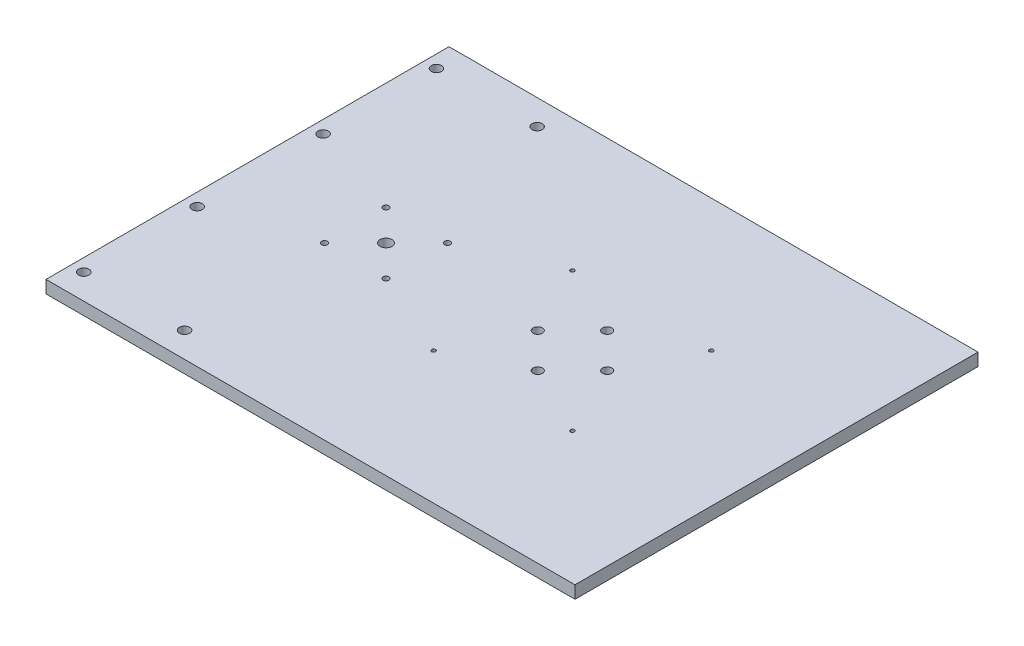
SolidWorks part; units mm, degrees
ref_plane "Front Plane" through (0, 0, 0) normal (0, 0, 1) x (1, 0, 0)
ref_plane "Top Plane" through (0, 0, 0) normal (0, 1, 0) x (1, 0, 0)
ref_plane "Right Plane" through (0, 0, 0) normal (1, 0, 0) x (0, 0, -1)
sketch "Sketch1" plane through (0, 0, 0) normal (0, 1, 0) x (1, 0, 0)
  line L1 (-133.35, -101.6) -> (133.35, -101.6)
  line L2 (-133.35, -101.6) -> (-133.35, 101.6)
  line L3 (-133.35, 101.6) -> (133.35, 101.6)
  line L4 (133.35, -101.6) -> (133.35, 101.6)
  line L5 (-133.35, -101.6) -> (133.35, 101.6) construction
  line L6 (-133.35, 101.6) -> (133.35, -101.6) construction
  point P0 (0, 0)
  dimension "D1" = 203.2
  dimension "D2" = 266.7
extrude "Boss-Extrude1" add sketch "Sketch1" along normal blind 6.35
sketch "Sketch2" plane through (0, 0, 0) normal (0, 1, 0) x (1, 0, 0)
  line L0 (-193.2668, 0) -> (192.9727, 0) construction
sketch "Sketch3" plane through (0, 6.35, 0) normal (0, 1, 0) x (1, 0, 0)
  circle A1 centre (-127, -31.75) radius 2.6
  circle A2 centre (-127, -31.75) radius 2.6
  circle A3 centre (-76.2, -88.9) radius 2.6
  circle A4 centre (-76.2, -88.9) radius 2.6
  circle A5 centre (-127, -88.9) radius 2.6
  circle A6 centre (-127, -88.9) radius 2.6
  dimension "D1" = 0
  dimension "D2" = 0
  dimension "D3" = 0
sketch "Sketch5" plane through (0, 6.35, 0) normal (0, 1, 0) x (1, 0, 0)
  circle A0 centre (-48.024, 15.5) radius 1.5 construction
  circle A1 centre (-48.024, -15.5) radius 1.5 construction
  circle A2 centre (-79.024, 15.5) radius 1.5 construction
  circle A3 centre (-79.024, -15.5) radius 1.5 construction
  circle A4 centre (-63.524, 0) radius 2.5 construction
  circle A5 centre (-48.024, 15.5) radius 1.5
  circle A6 centre (-48.024, -15.5) radius 1.5
  circle A7 centre (-79.024, 15.5) radius 1.5
  circle A8 centre (-79.024, -15.5) radius 1.5
  circle A9 centre (-63.524, 0) radius 2.5 construction
  circle A10 centre (-63.524, 0) radius 3.008
  dimension "D1" = 6.016
sketch "Sketch7" plane through (0, 6.35, 0) normal (0, 1, 0) x (1, 0, 0)
  circle A0 centre (65.4818, -35.0018) radius 1 construction
  circle A1 centre (-4.5218, -35.0018) radius 1 construction
  circle A2 centre (65.4818, -35.0018) radius 1
  circle A3 centre (-4.5218, -35.0018) radius 1
  circle A4 centre (-4.5218, 35.0018) radius 1 construction
  circle A5 centre (65.4818, 35.0018) radius 1 construction
  circle A6 centre (-4.5218, 35.0018) radius 1
  circle A7 centre (65.4818, 35.0018) radius 1
extrude "Cut-Extrude1" cut sketch "Sketch3" against normal through all
mirror "Mirror1" about plane through (0, 0, 0) normal (0, 0, 1) of "Cut-Extrude1"
extrude "Cut-Extrude2" cut sketch "Sketch5" against normal through all
extrude "Cut-Extrude3" cut sketch "Sketch7" against normal through all
sketch "Sketch8" plane through (0, 6.35, 0) normal (0, 1, 0) x (1, 0, 0)
  arc A0 (30.48, -19.85) -> (30.48, -15.15) centre (30.48, -17.5) ccw construction
  arc A1 (30.48, -19.85) -> (30.48, -15.15) centre (30.48, -17.5) ccw
  arc A2 (30.48, -15.15) -> (30.48, -19.85) centre (30.48, -17.5) ccw construction
  arc A3 (30.48, -15.15) -> (30.48, -19.85) centre (30.48, -17.5) ccw
  circle A4 centre (12.98, 0) radius 2.35 construction
  circle A5 centre (12.98, 0) radius 2.35
  arc A6 (30.48, 15.15) -> (30.48, 19.85) centre (30.48, 17.5) ccw construction
  arc A7 (30.48, 15.15) -> (30.48, 19.85) centre (30.48, 17.5) ccw
  arc A8 (30.48, 19.85) -> (30.48, 15.15) centre (30.48, 17.5) ccw construction
  arc A9 (30.48, 19.85) -> (30.48, 15.15) centre (30.48, 17.5) ccw
  circle A10 centre (47.98, 0) radius 2.35 construction
  circle A11 centre (47.98, 0) radius 2.35
extrude "Cut-Extrude4" cut sketch "Sketch8" against normal through all
equation "\"tightTol\" = 0.005in"
equation "\"normTol\" = 0.01in"
equation "\"looseTol\" = 0.02in"
equation "\"D1@Sketch5\"=5mm+2*\"looseTol\""
